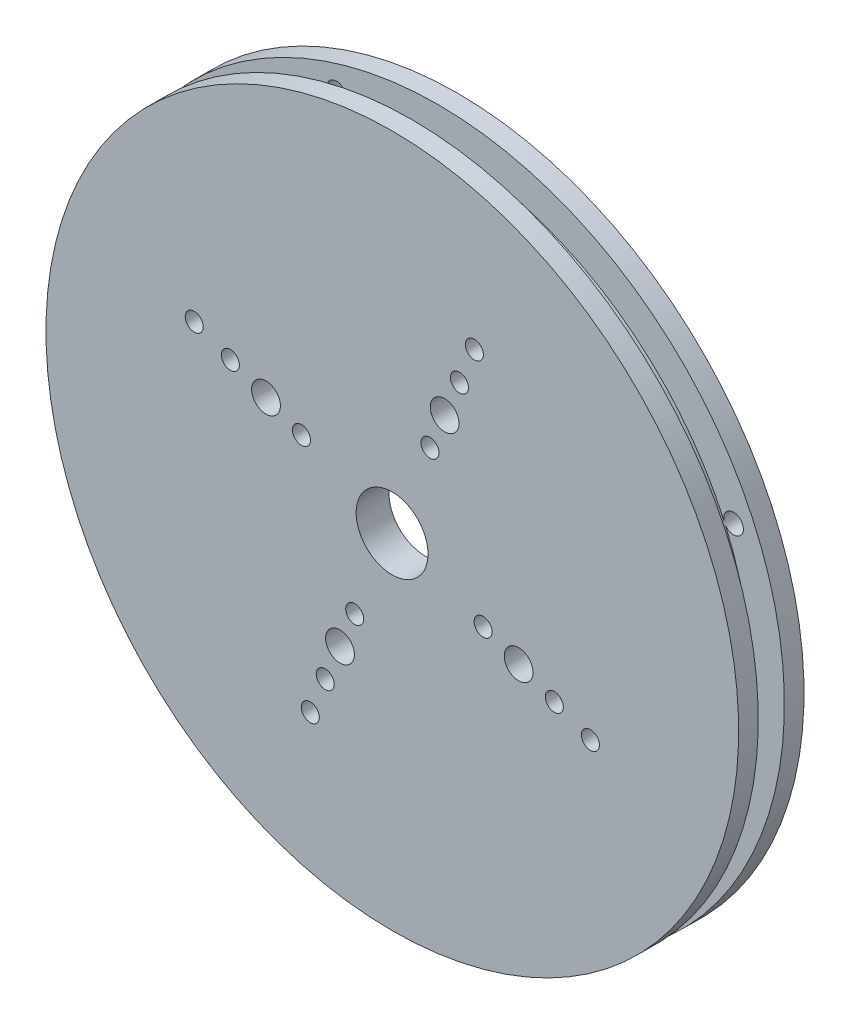
SolidWorks part; units mm, degrees
ref_plane "Plan de face" through (0, 0, 0) normal (0, 0, 1) x (1, 0, 0)
ref_plane "Plan de dessus" through (0, 0, 0) normal (0, 1, 0) x (1, 0, 0)
ref_plane "Plan de droite" through (0, 0, 0) normal (1, 0, 0) x (0, 0, -1)
sketch "Esquisse1" plane through (0, 0, 1.6866) normal (1, 0, 0) x (0, 0, -1)
  line L1 (0.1714, -3) -> (-1.8286, -3)
  line L2 (0.1714, -3) -> (0.1714, 21)
  line L3 (0.1714, 21) -> (-1.8286, 21)
  line L4 (-1.8286, -3) -> (-1.8286, 21)
  line L13 (1.6714, -3) -> (0.1714, -3)
  line L14 (1.6714, -3) -> (1.6714, 23.5)
  line L15 (1.6714, 23.5) -> (0.1714, 23.5)
  line L16 (0.1714, -3) -> (0.1714, 23.5)
  line L17 (-1.8286, 23.5) -> (-3.3286, 23.5)
  line L18 (-1.8286, 23.5) -> (-1.8286, -3)
  line L19 (-1.8286, -3) -> (-3.3286, -3)
  line L20 (-3.3286, 23.5) -> (-3.3286, -3)
  dimension "D1" = 1.5
  dimension "D2" = 1.5
  dimension "D3" = 2
  dimension "D4" = 24
  dimension "D5" = 26.5
revolve "Révolution1" add sketch "Esquisse1" angle 360 about L1 region at (0, 9, 2.5152) region at (0, 10.25, 0.7652) region at (0, 10.25, 4.2652)
sketch "Esquisse2" plane through (0, 0, 5.0152) normal (0, 0, 1) x (1, 0, 0)
  line L0 (26.4977, -3.351) -> (-26.5, -3) construction
  circle A0 centre (-0.0182, -3.1754) radius 2.75
  circle A1 centre (0, -3) radius 26.5 construction
  point P7 (0, 0)
  point P8 (0, 0)
extrude "Enlèv. mat.-Extru.1" cut sketch "Esquisse2" against normal blind 10
sketch "Esquisse13" plane through (0, 0, 0) normal (0, 0, 1) x (1, 0, 0)
  line L0 (-122.2352, 39.9508) -> (-38.6976, 41.258) construction
  line L1 (-36.0992, -44.5996) -> (67.3726, -4.8805) construction
  line L4 (15.1562, -9.278) -> (-15.1562, 3.278) construction
  line L5 (-6.278, -18.1562) -> (6.278, 12.1562) construction
  circle A2 centre (-2.8778, -9.9476) radius 0.6896
  circle A3 centre (6.9476, -5.8778) radius 0.6896
  circle A4 centre (9.6638, -7.0029) radius 1.1
  circle A5 centre (12.3938, -8.1338) radius 0.6896
  circle A6 centre (15.1562, -9.278) radius 0.6896
  circle A7 centre (2.8778, 3.9476) radius 0.6896
  circle A8 centre (4.0029, 6.6638) radius 1.1
  circle A9 centre (5.1338, 9.3938) radius 0.6896
  circle A10 centre (6.278, 12.1562) radius 0.6896
  circle A11 centre (-4.0029, -12.6638) radius 1.1
  circle A12 centre (-5.1338, -15.3938) radius 0.6896
  circle A13 centre (-6.278, -18.1562) radius 0.6896
  circle A14 centre (-6.9476, -0.1222) radius 0.6896
  circle A15 centre (-9.6638, 1.0029) radius 1.1
  circle A16 centre (-12.3938, 2.1338) radius 0.6896
  circle A17 centre (-15.1562, 3.278) radius 0.6896
  circle A19 centre (0, -3) radius 7.52 construction
  circle A20 centre (0, -3) radius 10.46 construction
  circle A21 centre (0, -3) radius 13.415 construction
  circle A22 centre (0, -3) radius 16.405 construction
  point P0 (0, 0)
sketch "Esquisse14" plane through (0, 0, 0) normal (0, 0, 1) x (1, 0, 0)
  line L0 (-122.2352, 39.9508) -> (-38.6976, 41.258) construction
  line L1 (-36.0992, -44.5996) -> (67.3726, -4.8805) construction
  spline S0 degree 2 poles (6.7095, 2.7436) (4.5975, -1.3195) (9.1051, -2.6286) knots 0 0 0 1 1 1 construction
  spline S1 degree 3 poles (-0.5608, 5.6062) (1.1805, 8.2527) (2.8687, 10.4384) (5.1281, 13.8669) (7.0874, 14.3139) (8.3916, 12.6802) (7.2661, 8.5047) (7.0552, 4.6338) (6.7095, 2.7436) knots 0 0 0 0 0.368171 0.418118 0.499474 0.581227 0.63128 1 1 1 1 construction
  spline S2 degree 2 poles (-0.5608, 5.6062) (-1.8662, 1.4438) (-5.8382, 3.5619) knots 0 0 0 1 1 1 construction
  spline S3 degree 3 poles (9.1051, -2.6286) (11.376, -4.297) (13.9367, -6.0338) (16.9471, -8.1818) (17.3829, -10.0409) (15.6763, -11.2158) (11.6017, -10.1948) (8.3971, -9.8909) (5.7682, -9.4912) knots 0 0 0 0 0.365231 0.41369 0.484595 0.573039 0.62458 1 1 1 1 construction
  spline S4 degree 2 poles (5.7682, -9.4912) (2.1673, -7.506) (0.914, -11.3287) knots 0 0 0 1 1 1 construction
  spline S5 degree 3 poles (0.914, -11.3287) (-1.3562, -14.5677) (-2.4297, -16.1534) (-4.9925, -19.7972) (-7.106, -20.4883) (-8.0922, -18.5459) (-7.4183, -14.316) (-7.0267, -12.3758) (-6.3958, -8.7367) knots 0 0 0 0 0.370191 0.421117 0.509255 0.593778 0.642852 1 1 1 1 construction
  spline S6 degree 2 poles (-6.3958, -8.7367) (-4.4116, -4.9383) (-8.4827, -3.685) knots 0 0 0 1 1 1 construction
  spline S7 degree 3 poles (-8.4827, -3.685) (-11.9491, -1.3363) (-13.5133, -0.3098) (-16.9826, 2.3011) (-16.9406, 4.3561) (-15.2444, 5.1901) (-10.9497, 4.5175) (-8.5569, 4.0332) (-5.8382, 3.5619) knots 0 0 0 0 0.388588 0.439956 0.513686 0.605056 0.653688 1 1 1 1 construction
  spline S8 degree 1 poles (-0.8345, 5.7361) (-5.7395, 3.8493) knots 0 0 1 1 construction
  spline S9 degree 1 poles (-8.6139, -3.9586) (-5.7395, 3.8493) knots 0 0 1 1 construction
  spline S10 degree 1 poles (-6.6834, -8.6393) (-8.6139, -3.9586) knots 0 0 1 1 construction
  spline S11 degree 1 poles (1.1852, -11.4645) (-6.6834, -8.6393) knots 0 0 1 1 construction
  spline S12 degree 1 poles (5.6702, -9.7797) (1.1852, -11.4645) knots 0 0 1 1 construction
  spline S13 degree 1 poles (9.2399, -2.3554) (5.6702, -9.7797) knots 0 0 1 1 construction
  spline S14 degree 1 poles (6.9965, 2.6453) (9.2399, -2.3554) knots 0 0 1 1 construction
  spline S15 degree 1 poles (-0.8345, 5.7361) (6.9965, 2.6453) knots 0 0 1 1 construction
  spline S16 degree 2 poles (-0.8345, 5.7361) (-1.3236, 4.2068) (-2.6043, 3.2067) (-4.2666, 3.072) (-5.7395, 3.8493) knots -0.004811 -0.004811 -0.004811 0.373998 0.626538 1.005348 1.005348 1.005348
  spline S17 degree 3 poles (-5.7395, 3.8493) (-6.2151, 3.9317) (-7.1851, 4.1035) (-8.5214, 4.3474) (-9.8525, 4.5913) (-11.2133, 4.8349) (-12.4217, 5.0437) (-13.4517, 5.2099) (-14.2791, 5.3495) (-15.1763, 5.3548) (-16.0151, 5.0974) (-16.7156, 4.5962) (-17.1548, 3.816) (-17.2469, 2.9159) (-16.9724, 2.0275) (-16.3347, 1.4225) (-15.7222, 0.9845) (-15.1601, 0.5645) (-14.4443, 0.0444) (-13.597, -0.5611) (-12.5732, -1.2728) (-11.4658, -2.0289) (-10.3988, -2.7508) (-9.435, -3.4026) (-8.8816, -3.7772) (-8.6139, -3.9586) knots -0.001388 -0.001388 -0.001388 -0.001388 0.061325 0.124038 0.18675 0.249463 0.312175 0.343532 0.374888 0.406244 0.437601 0.468957 0.500313 0.53167 0.563026 0.594382 0.625739 0.657095 0.688451 0.751164 0.813876 0.876589 0.939302 0.970658 1.002014 1.002014 1.002014 1.002014
  spline S18 degree 2 poles (-8.6139, -3.9586) (-7.1152, -4.4284) (-6.1191, -5.6542) (-5.9577, -7.2336) (-6.6834, -8.6393) knots -0.005465 -0.005465 -0.005465 0.373559 0.626242 1.005266 1.005266 1.005266
  spline S19 degree 3 poles (-6.6834, -8.6393) (-6.7365, -8.9456) (-6.8467, -9.5773) (-7.0427, -10.6867) (-7.2659, -11.9301) (-7.5064, -13.2594) (-7.7338, -14.5378) (-7.9261, -15.6428) (-8.082, -16.6025) (-8.2179, -17.3704) (-8.2866, -18.2563) (-8.0649, -19.167) (-7.5956, -19.9388) (-6.8052, -20.4093) (-5.903, -20.3614) (-5.0536, -20.0041) (-4.3484, -19.3959) (-3.7001, -18.4845) (-3.0206, -17.5077) (-2.2697, -16.4295) (-1.5425, -15.3799) (-0.7725, -14.2696) (-0.0397, -13.2162) (0.6214, -12.2695) (1.0012, -11.727) (1.1852, -11.4645) knots -0.001388 -0.001388 -0.001388 -0.001388 0.029952 0.061293 0.123974 0.186655 0.249336 0.312017 0.343358 0.374698 0.406039 0.43738 0.46872 0.500061 0.531401 0.562742 0.594082 0.625423 0.688104 0.750785 0.813466 0.876147 0.938829 0.970169 1.00151 1.00151 1.00151 1.00151
  spline S20 degree 2 poles (1.1852, -11.4645) (1.6549, -10.0593) (2.8294, -9.1584) (4.3345, -9.0507) (5.6702, -9.7797) knots -0.006505 -0.006505 -0.006505 0.373008 0.626017 1.005531 1.005531 1.005531
  spline S21 degree 3 poles (5.6702, -9.7797) (6.5695, -9.9164) (7.9012, -10.0932) (9.7591, -10.3475) (11.1725, -10.5612) (12.369, -10.7706) (13.3391, -10.9668) (14.0651, -11.124) (14.8219, -11.319) (15.7086, -11.3124) (16.5342, -10.937) (17.1821, -10.3101) (17.4648, -9.4297) (17.3189, -8.5471) (16.8686, -7.7861) (16.2466, -7.3076) (15.6668, -6.9045) (14.8845, -6.3515) (13.9112, -5.6724) (12.7425, -4.8563) (11.1877, -3.7652) (10.0127, -2.9232) (9.2399, -2.3554) knots -0.002298 -0.002298 -0.002298 -0.002298 0.123304 0.186105 0.248906 0.311707 0.343107 0.374508 0.405908 0.437309 0.468709 0.50011 0.53151 0.562911 0.594311 0.625712 0.657112 0.688513 0.751314 0.814115 0.876916 1.002518 1.002518 1.002518 1.002518
  spline S22 degree 2 poles (9.2399, -2.3554) (7.5706, -1.8635) (6.4345, -0.548) (6.2248, 1.1415) (6.9965, 2.6453) knots -0.004925 -0.004925 -0.004925 0.374047 0.626695 1.005666 1.005666 1.005666
  spline S23 degree 3 poles (6.9965, 2.6453) (7.028, 2.8173) (7.0839, 3.1488) (7.1937, 3.9233) (7.3237, 5.0061) (7.494, 6.4638) (7.6993, 8.0218) (7.9171, 9.3576) (8.1305, 10.428) (8.3105, 11.208) (8.5229, 12.0338) (8.3984, 12.963) (7.885, 13.7297) (6.857, 14.4307) (5.5694, 14.3145) (4.6084, 13.6014) (4.1464, 12.9286) (3.7376, 12.3158) (3.1863, 11.5143) (2.5114, 10.5517) (1.703, 9.4162) (0.8836, 8.2606) (0.0505, 7.0631) (-0.5468, 6.1733) (-0.8345, 5.7361) knots -0.001626 -0.001626 -0.001626 -0.001626 0.029765 0.061156 0.123938 0.18672 0.249502 0.312284 0.343675 0.375066 0.406457 0.437848 0.469239 0.50063 0.563412 0.594802 0.626193 0.657584 0.688975 0.751757 0.814539 0.877321 0.940103 1.002885 1.002885 1.002885 1.002885
  dimension "D1" = 0.3
extrude "Enlèv. mat.-Extru.4" cut sketch "Esquisse13" along normal blind 10
extrude "Enlèv. mat.-Extru.5" cut sketch "Esquisse14" along normal blind 2.5
sketch "Esquisse15" plane through (0, 0, 0.0152) normal (0, 0, -1) x (-1, 0, 0)
  circle A0 centre (-22.6094, 7.0394) radius 0.75
  circle A2 centre (24.1461, -9.0231) radius 0.75
  circle A3 centre (7.7697, 20.4099) radius 0.75
  circle A4 centre (-10.5022, -25.6625) radius 0.75
  circle A5 centre (0.0182, -3.1754) radius 24.8264 construction
  point P2 (0, 0)
  point P3 (0, 0)
  point P11 (0, 0)
extrude "Enlèv. mat.-Extru.6" cut sketch "Esquisse15" against normal blind 2 contours A2 | A3 | A0 | A4
